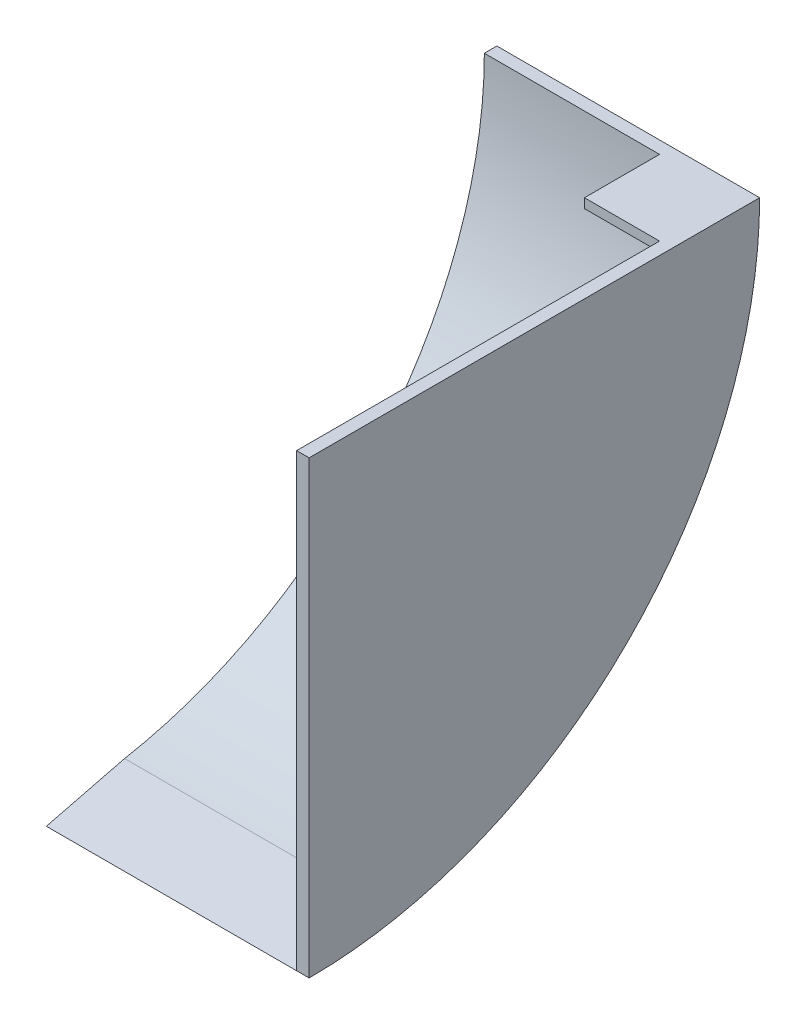
SolidWorks part; units mm, degrees
material "6061 Alloy"
ref_plane "Front Plane" through (0, 0, 0) normal (0, 0, 1) x (1, 0, 0)
ref_plane "Top Plane" through (0, 0, 0) normal (0, 1, 0) x (1, 0, 0)
ref_plane "Right Plane" through (0, 0, 0) normal (1, 0, 0) x (0, 0, -1)
sketch "Sketch2" plane through (0, 0, 0) normal (1, 0, 0) x (0, 0, -1)
  line L0 (175, 0) -> (180, 0)
  line L1 (0, -175) -> (0, -180)
  arc A0 (0, -180) -> (180, 0) centre (0, 0) ccw
  arc A1 (0, -175) -> (175, 0) centre (0, 0) ccw
  dimension "D1" = 360
  dimension "D2" = 350
extrude "Boss-Extrude1" add sketch "Sketch2" along normal blind 100
sketch "Sketch3" plane through (100, 0, 0) normal (1, 0, 0) x (0, 0, -1)
  line L0 (0, 0) -> (0, -180)
  line L5 (180, 0) -> (0, 0)
  arc A0 (180, 0) -> (0, -180) centre (0, 0) cw
  arc A1 (0, -180) -> (180, 0) centre (0, 0) ccw construction
  dimension "D1" = 180
extrude "Boss-Extrude2" add sketch "Sketch3" along normal blind 5
chamfer "Chamfer1" distance 20 distance2 5 1 edges at (50, -175, 0) first distance on face at (50, -105.6218, -105.6218)
sketch "Sketch4" plane through (100, 0, 0) normal (-1, 0, 0) x (0, 0, 1)
  line L0 (-175, 0) -> (-145, 0)
  line L1 (-145, 0) -> (-145, -3.7623)
  line L2 (-145, -3.7623) -> (-175, -3.7623)
  line L3 (-175, -3.7623) -> (-175, 0)
extrude "Boss-Extrude3" add sketch "Sketch4" along normal blind 30
